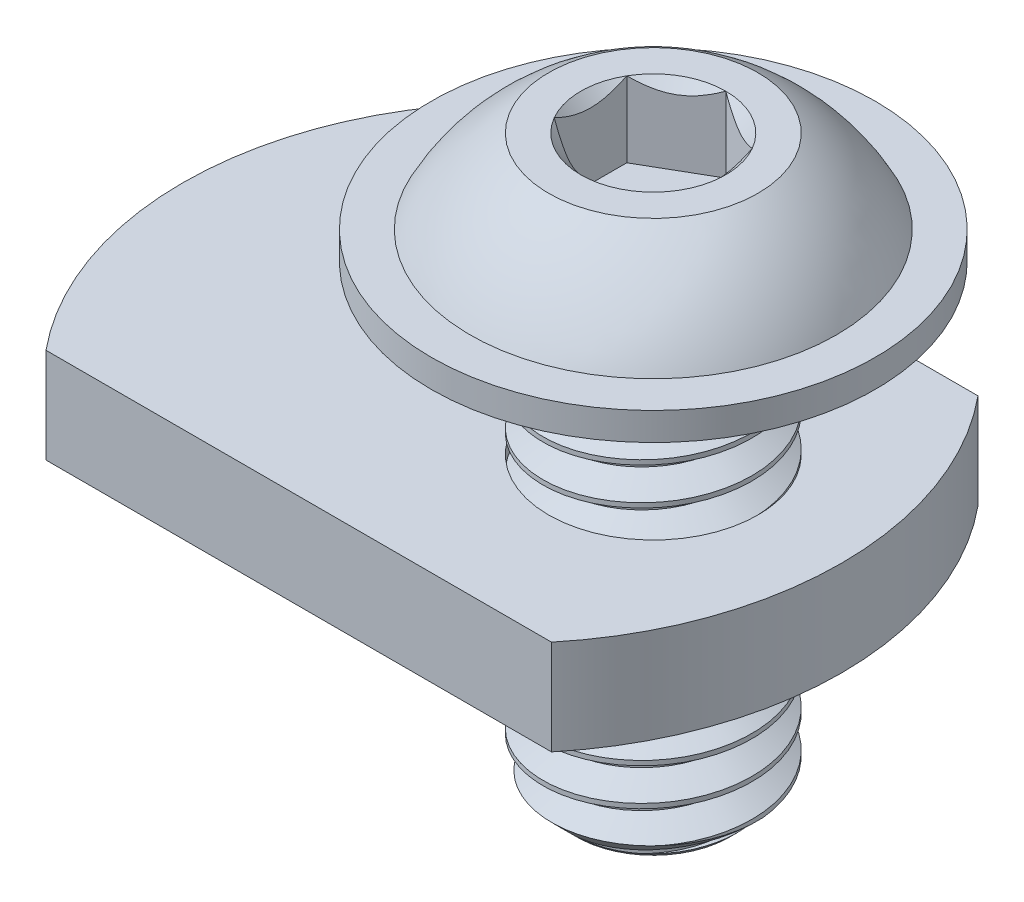
SolidWorks part; units mm, degrees
ref_plane "Front Plane" through (0, 0, 0) normal (0, 0, 1) x (1, 0, 0)
ref_plane "Top Plane" through (0, 0, 0) normal (0, 1, 0) x (1, 0, 0)
ref_plane "Right Plane" through (0, 0, 0) normal (1, 0, 0) x (0, 0, -1)
sketch "Sketch1" plane through (0, 0, 0) normal (0, 1, 0) x (1, 0, 0)
  circle A0 centre (0, 0) radius 3.9688
  point P3 (-3.9688, 0)
  point P4 (3.9688, 0)
  dimension "D1" = 7.9375
extrude "Boss-Extrude1" add sketch "Sketch1" against normal blind 17.4625
sketch "Sketch2" plane through (0, -17.4625, 0) normal (0, -1, 0) x (1, 0, 0)
  circle A1 centre (0, 0) radius 3.9688
  circle A2 centre (0, 0) radius 3.9688
  point P0 (0, -3.9688)
  dimension "D1" = 0
curve "Helix/Spiral1" pitch 1.4111 height 18.8736 turns 13.375
sketch "Sketch3" plane through (0, 0, 0) normal (1, 0, 0) x (0, 0, -1)
  line L0 (4.1215, -17.3743) -> (2.8994, -18.0799) construction
  line L1 (2.8994, -18.0799) -> (4.1215, -18.7854) construction
  line L2 (4.1215, -18.7854) -> (4.1215, -17.3743) construction
  line L3 (3.0522, -17.9917) -> (3.0522, -18.1681) construction
  line L4 (3.9688, -17.4625) -> (3.9688, -18.6972) construction
  line L5 (2.8994, -18.0799) -> (3.0522, -18.0799) construction
  line L6 (3.9688, -18.0799) -> (4.1215, -18.0799) construction
  line L8 (2.8994, -18.0799) -> (-3.9688, -18.0799) construction
  line L9 (3.0522, -17.9917) -> (4.0451, -17.4184)
  line L10 (3.0522, -17.9917) -> (3.0522, -18.1681)
  line L11 (3.0522, -18.1681) -> (4.0451, -18.7413)
  line L12 (4.0451, -18.7413) -> (4.0451, -17.4184)
  line L14 (-3.9688, -18.0799) -> (-3.9688, -16.6687) construction
  line L15 (-3.9688, -16.6687) -> (-3.9688, -15.2576) construction
  line L16 (-3.9688, -15.2576) -> (-3.9687, -13.8465) construction
  line L17 (-3.9687, -13.8465) -> (-3.9688, -12.4354) construction
  line L18 (-3.9688, 0) -> (-3.9688, -17.4625) construction
  point P15 (4.0451, -18.0799)
  dimension "D1" = 1.4111
  dimension "D2" = 0.1764
sweep "Cut-Sweep1" cut profiles "Sketch3" path "Helix/Spiral1"
sketch "Sketch4" plane through (0, -17.4625, 0) normal (0, -1, 0) x (1, 0, 0)
  circle A0 centre (0, 0) radius 2.8994
extrude "Cut-Extrude1" cut sketch "Sketch4" against normal blind 1.4111 draft 45 flip side to cut
sketch "Sketch5" plane through (0, 0, 0) normal (0, 0, 1) x (1, 0, 0)
  line L0 (0, 0) -> (0, 4.2164)
  line L1 (-8.4201, 0) -> (0, 0)
  line L2 (0, 4.2164) -> (-3.9688, 4.2164)
  line L3 (-6.9469, 1.0541) -> (-8.4201, 1.0541)
  line L4 (-8.4201, 1.0541) -> (-8.4201, 0)
  line L5 (0, 0) -> (0, -17.4625) construction
  arc A0 (-3.9688, 4.2164) -> (-6.9469, 1.0541) centre (0, -2.5047) ccw
  dimension "D1" = 4.2164
  dimension "D2" = 1.0541
  dimension "D3" = 16.8402
  dimension "D4" = 13.8938
revolve "Revolve1" add sketch "Sketch5" angle 360 mid plane about L0
sketch "Sketch6" plane through (0, 4.2164, 0) normal (0, 1, 0) x (1, 0, 0)
  line L1 (0, 2.7496) -> (-2.3813, 1.3748)
  line L2 (-2.3813, 1.3748) -> (-2.3812, -1.3748)
  line L3 (-2.3812, -1.3748) -> (0, -2.7496)
  line L4 (0, -2.7496) -> (2.3813, -1.3748)
  line L5 (2.3813, -1.3748) -> (2.3812, 1.3748)
  line L6 (2.3812, 1.3748) -> (0, 2.7496)
  circle A0 centre (0, 0) radius 2.3813 construction
  dimension "D1" = 4.7625
extrude "Cut-Extrude2" cut sketch "Sketch6" against normal blind 2.8575
sketch "Sketch7" plane through (0, 4.2164, 0) normal (0, 1, 0) x (1, 0, 0)
  circle A0 centre (0, 0) radius 2.7496
extrude "Cut-Extrude3" cut sketch "Sketch7" against normal blind 2.8575 draft 45
sketch "Sketch8" plane through (0, 0, 0) normal (0, 1, 0) x (1, 0, 0)
  line L0 (-17.8562, 0) -> (0, 0) construction
  line L1 (0, 0) -> (7.1374, 0) construction
  line L2 (-14.9462, 8.0899) -> (4.2274, 8.0899)
  line L3 (-14.9462, -8.0899) -> (4.2274, -8.0899)
  line L4 (-17.8562, 8.0899) -> (7.1374, 8.0899) construction
  line L5 (-17.8562, 8.0899) -> (-17.8562, -8.0899) construction
  line L6 (-17.8562, -8.0899) -> (7.1374, -8.0899) construction
  line L7 (7.1374, 8.0899) -> (7.1374, -8.0899) construction
  arc A0 (-14.9462, 8.0899) -> (-14.9462, -8.0899) centre (-5.1562, 0) ccw
  arc A1 (4.2274, 8.0899) -> (4.2274, -8.0899) centre (-5.5626, 0) cw
  circle A3 centre (0, 0) radius 3.9688
  circle A4 centre (0, 0) radius 3.9688
  dimension "D2" = 24.9936
  dimension "D5" = 12.7
  dimension "D6" = 12.7
  dimension "D3" = 16.1798
  dimension "D4" = 7.1374
  dimension "D1" = 0
extrude "Boss-Extrude2" add sketch "Sketch8" against normal blind 3.6068 from offset 6.35 separate body offset against normal yes
sketch "Sketch9" plane through (0, -9.9568, 0) normal (0, -1, 0) x (1, 0, 0)
  circle A1 centre (0, 0) radius 3.9688 construction
  circle A2 centre (0, 0) radius 3.9688
  circle A3 centre (0, 0) radius 4.5593
  dimension "D1" = 9.1186
extrude "Boss-Extrude3" add sketch "Sketch9" along normal blind 2.032
sketch "SketchZ" plane through (0, 0, 0) normal (0, 0, 1) x (1, 0, 0)
  line L0 (3.9688, -17.7271) -> (3.9688, -16.316) construction
  line L2 (0, -18.0799) -> (0, -16.6687) construction
  line L4 (3.9688, -17.7271) -> (0, -17.7271) construction
  line L5 (0, -13.8465) -> (0, -12.4354) construction
  line L6 (0, -17.3743) -> (0, -18.0799) construction
equation "\"D3@Helix/Spiral1\" = \"D4@Helix/Spiral1\" + \"D1@Boss-Extrude1\""
equation "\"D1@Sketch3\" = \"D4@Helix/Spiral1\""
equation "\"D2@Sketch3\" = \"D1@Sketch3\" / 8"
equation "\"D1@Cut-Extrude1\" = \"D4@Helix/Spiral1\""
equation "\"D1@Cut-Extrude2\" = \"D1@Sketch6\" * 3/5"
equation "\"D1@Cut-Extrude3\" = \"D1@Cut-Extrude2\""
equation "\"D2@Sketch5\" = \"D1@Sketch5\" * 1/4"
